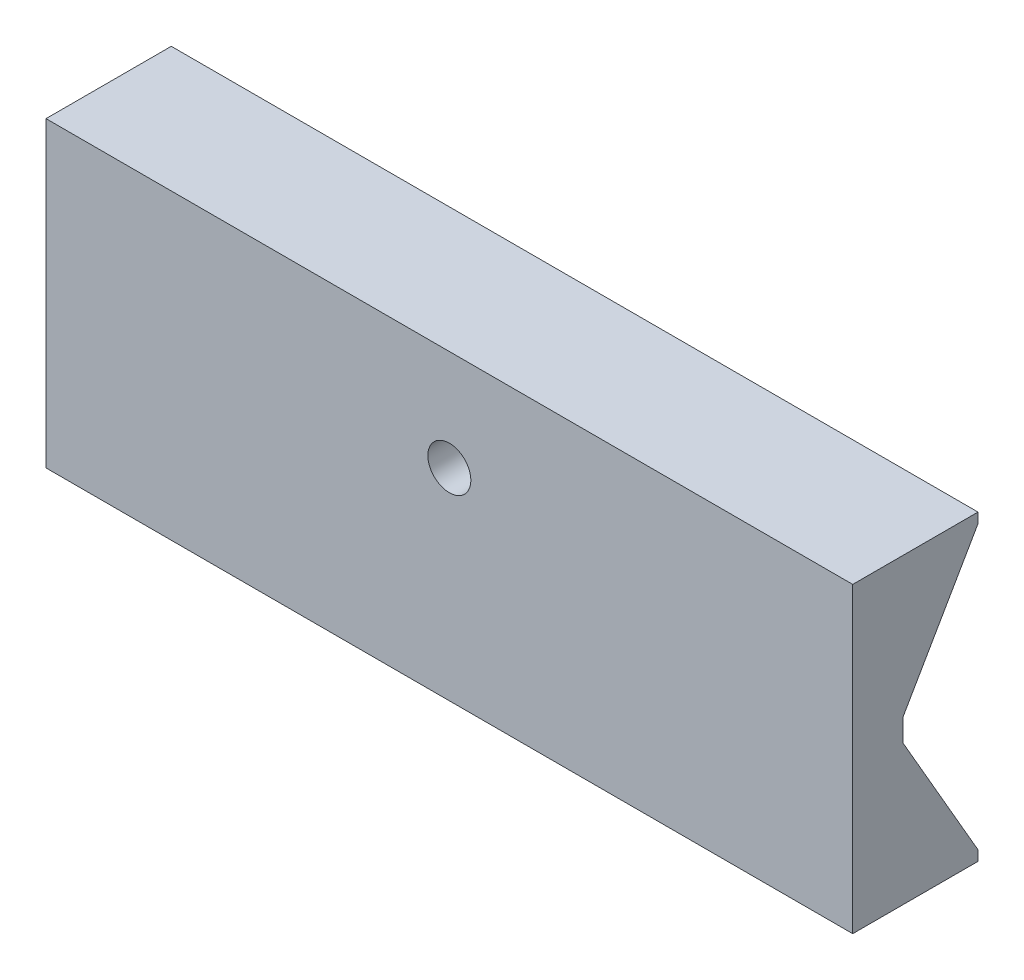
SolidWorks part; units mm, degrees
material "6061 Alloy"
ref_plane "Front Plane" through (0, 0, 0) normal (0, 0, 1) x (1, 0, 0)
ref_plane "Top Plane" through (0, 0, 0) normal (0, 1, 0) x (1, 0, 0)
ref_plane "Right Plane" through (0, 0, 0) normal (1, 0, 0) x (0, 0, -1)
sketch "Sketch1" plane through (0, 0, 0) normal (1, 0, 0) x (0, 0, -1)
  line L0 (0, -19.05) -> (16.51, -19.05) construction
  line L1 (16.51, -19.05) -> (6.35, -1.4524) construction
  line L2 (6.35, 1.4524) -> (16.51, 19.05) construction
  line L3 (16.51, 19.05) -> (0, 19.05) construction
  line L4 (0, 19.05) -> (0, -19.05)
  line L5 (6.35, 1.4524) -> (15.7768, 17.78)
  line L6 (0, 0) -> (6.35, 0) construction
  line L7 (6.35, 1.4524) -> (6.35, -1.4524)
  line L8 (15.7768, 17.78) -> (15.7768, 19.05)
  line L9 (6.35, -1.4524) -> (15.7768, -17.78)
  line L10 (15.7768, -17.78) -> (15.7768, -19.05)
  line L11 (15.7768, 19.05) -> (0, 19.05)
  line L12 (0, -19.05) -> (15.7768, -19.05)
  circle A0 centre (20.1762, 0) radius 12.7 construction
  dimension "D5" = 25.4
  dimension "D1" = 38.1
  dimension "D2" = 120
  dimension "D3" = 6.35
  dimension "D4" = 10.16
  dimension "D6" = 1.27
extrude "Boss-Extrude1" add sketch "Sketch1" along normal blind 101.6
hole_wizard "1/4-28 Tapped Hole1" positions "Sketch3" profile "Sketch2" tap size "1/4-28" standard "ANSI Inch" end condition through all
sketch "Sketch3" plane through (0, 0, 0) normal (0, 0, 1) x (1, 0, 0)
  line L0 (50.8, 19.05) -> (50.8, -19.05) construction
  line L3 (101.6, 19.05) -> (0, 19.05) construction
  line L4 (101.6, 0) -> (0, 0) construction
  line L5 (101.6, 19.05) -> (101.6, -19.05) construction
  line L6 (0, 19.05) -> (0, -19.05) construction
  point P0 (50.8, 6.35)
  dimension "D1" = 6.35
sketch "Sketch2" plane through (50.8, 6.35, 0) normal (1, 0, 0) x (0, -1, 0)
  line L0 (0, 0) -> (0, 15.7768)
  line L1 (0, 15.7768) -> (2.7051, 15.7768)
  line L2 (2.7051, 15.7768) -> (2.7051, 0)
  line L5 (2.7051, 0) -> (0, 0)
  line L11 (0, -6.35) -> (0, 107.95) construction
  dimension "Thru Tap Drill Dia." = 5.4102
  dimension "Thru Tap Drill Depth" = 15.7768
cosmetic thread "Hole Thread1" parameters "D1"=9.1818, "D2"=6.35
equation "\"delta-z\" = 1.5"
equation "\"max-tube-diam\" = 3.5"
equation "\"v-block-notch-height\" = 1.5"
equation "\"v-block-notch-angle\" = 120"
equation "\"jaw-travel\" = 4.45"
equation "\"D1@Sketch1\"=\"v-block-notch-height\""
equation "\"D2@Sketch1\"=\"v-block-notch-angle\""
equation "\"total-height\" = 3.28"
equation "\"mid-height\" = 1.5"
equation "\"jaw-width\" = 4"
equation "\"jaw-height\" = \"total-height\" - \"mid-height\""
equation "\"jaw-mod-plate-thickness\" = .375"
equation "\"jaw-mod-height\" =  \"max-tube-diam\"/2 + \"delta-z\" + \"v-block-notch-height\"/2"
equation "\"rib-top-width\" = 0.5"
equation "\"rib-side-width\" = 0.5"
equation "\"quarter-twenty-close-clearance\" = .257"
equation "\"box-way-width\" = 1.5"
equation "\"box-way-depth\" = 1.5"
equation "\"screw-OD\" = .625"
equation "\"screw-reduced-diam\" = .47"
equation "\"pressure-plate-OD\" = 6.75"
equation "\"swivel-cleat-thick\" = .5"
equation "\"swivel-gap\" = .02"
equation "\"D1@Boss-Extrude1\"=\"jaw-width\""
